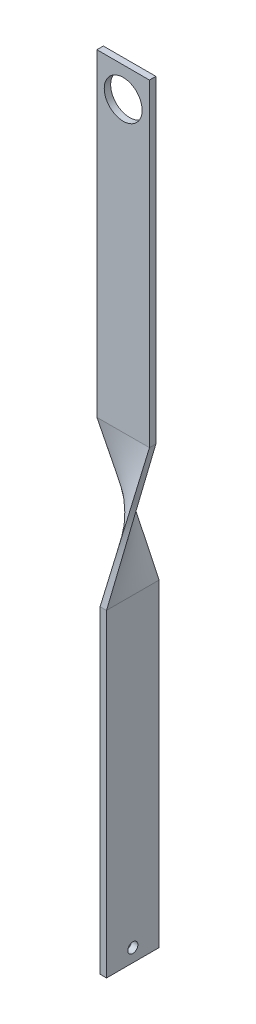
SolidWorks part; units mm, degrees
ref_plane "Front Plane" through (0, 0, 0) normal (0, 0, 1) x (1, 0, 0)
ref_plane "Top Plane" through (0, 0, 0) normal (0, 1, 0) x (1, 0, 0)
ref_plane "Right Plane" through (0, 0, 0) normal (1, 0, 0) x (0, 0, -1)
sketch "Sketch1" plane through (0, 0, 0) normal (0, 0, 1) x (1, 0, 0)
  line L1 (0, 0) -> (13.208, 0)
  line L2 (0, 0) -> (0, -80)
  line L3 (0, -80) -> (13.208, -80)
  line L4 (13.208, 0) -> (13.208, -80)
  dimension "D1" = 80
  dimension "D2" = 13.208
extrude "Boss-Extrude1" add sketch "Sketch1" along normal blind 1.6129
ref_plane "Plane1" through (6.604, 0, 0) normal (1, 0, 0) x (0, 0, -1)
sketch "Sketch2" plane through (6.604, 0, 0) normal (1, 0, 0) x (0, 0, -1)
  line L0 (-0.8065, -80) -> (-0.8065, 0) construction
  line L2 (-1.6129, 0) -> (0, 0) construction
  line L3 (-1.6129, -80) -> (0, -80) construction
  line L5 (-7.4104, -195) -> (5.7976, -195)
  line L6 (-7.4104, -195) -> (-7.4104, -115)
  line L7 (-7.4104, -115) -> (5.7976, -115)
  line L8 (5.7976, -195) -> (5.7976, -115)
  line L9 (-7.4104, -195) -> (5.7976, -115) construction
  line L10 (-7.4104, -115) -> (5.7976, -195) construction
  point P0 (-0.8065, -155)
  point P3 (-0.8065, -40)
  point P12 (0, 0)
  dimension "D1" = 13.208
  dimension "D2" = 80
  dimension "D3" = 35
extrude "Boss-Extrude2" add sketch "Sketch2" along normal blind 1.6129 separate body
loft "Loft2" add section face at (6.604, -80, 0.8065) section face at (7.4104, -115, 0.8064) connector at (13.208, -80, 1.6129) connector at (6.604, -115, 7.4104)
sketch "Sketch3" plane through (8.2169, 0, 0) normal (1, 0, 0) x (0, 0, -1)
  line L0 (-7.4104, -195) -> (5.7976, -195) construction
  circle A0 centre (-0.8064, -191.698) radius 1.27
  point P2 (-0.437, -189.6049)
  point P5 (-0.8064, -195)
  dimension "D1" = 3.302
  dimension "D2" = 2.54
extrude "Cut-Extrude1" cut sketch "Sketch3" against normal through all
sketch "Sketch4" plane through (0, 0, 0) normal (0, 0, -1) x (-1, 0, 0)
  line L0 (-13.208, 0) -> (0, 0) construction
  circle A0 centre (-6.604, -7.5) radius 4.7625
  point P2 (0, 0)
  point P5 (-6.604, 0)
  dimension "D1" = 7.5
  dimension "D2" = 9.525
extrude "Cut-Extrude2" cut sketch "Sketch4" against normal through all
